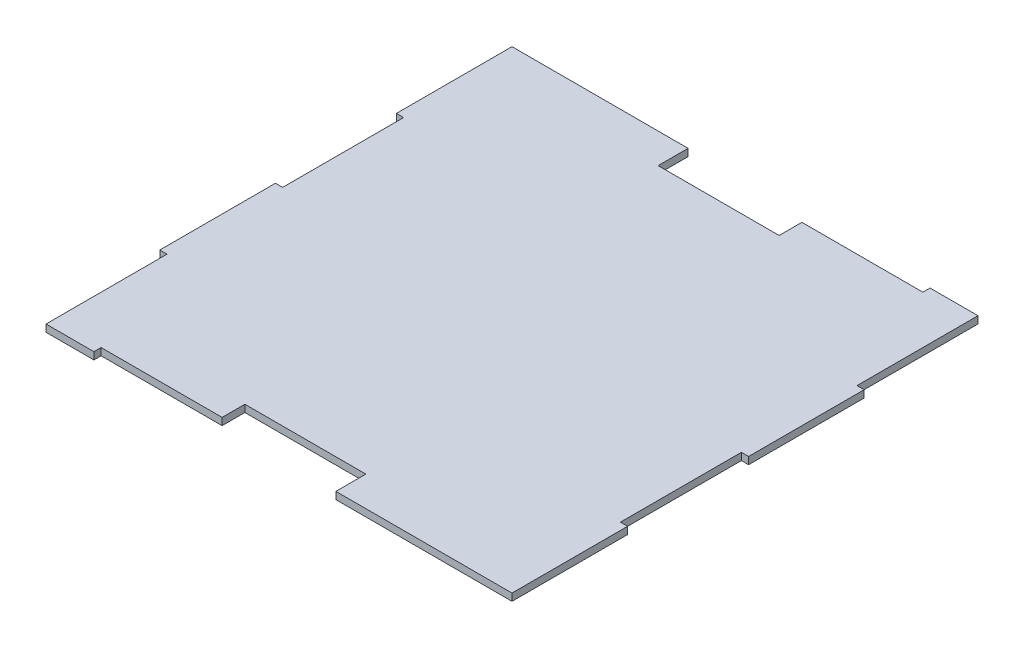
SolidWorks part; units mm, degrees
ref_plane "Front Plane" through (0, 0, 0) normal (0, 0, 1) x (1, 0, 0)
ref_plane "Top Plane" through (0, 0, 0) normal (0, 1, 0) x (1, 0, 0)
ref_plane "Right Plane" through (0, 0, 0) normal (1, 0, 0) x (0, 0, -1)
sketch "Sketch1" plane through (0, 0, 0) normal (0, 1, 0) x (1, 0, 0)
  line L1 (-197.5, -197.5) -> (197.5, -197.5)
  line L2 (-197.5, -197.5) -> (-197.5, 197.5)
  line L3 (-197.5, 197.5) -> (197.5, 197.5)
  line L4 (197.5, -197.5) -> (197.5, 197.5)
  line L5 (-197.5, -197.5) -> (197.5, 197.5) construction
  line L6 (-197.5, 197.5) -> (197.5, -197.5) construction
  line L7 (-50.5, 222.5) -> (50.5, 222.5)
  line L8 (-50.5, 222.5) -> (-50.5, 172.5)
  line L9 (-50.5, 172.5) -> (50.5, 172.5)
  line L10 (50.5, 222.5) -> (50.5, 172.5)
  line L11 (-50.5, 222.5) -> (50.5, 172.5) construction
  line L12 (-50.5, 172.5) -> (50.5, 222.5) construction
  line L13 (-50.5, -222.5) -> (50.5, -222.5)
  line L14 (-50.5, -222.5) -> (-50.5, -172.5)
  line L15 (-50.5, -172.5) -> (50.5, -172.5)
  line L16 (50.5, -222.5) -> (50.5, -172.5)
  line L17 (-50.5, -222.5) -> (50.5, -172.5) construction
  line L18 (-50.5, -172.5) -> (50.5, -222.5) construction
  line L43 (50.5, 197.5) -> (151.5, 197.5)
  line L44 (50.5, 197.5) -> (50.5, 191.5)
  line L45 (50.5, 191.5) -> (151.5, 191.5)
  line L46 (151.5, 197.5) -> (151.5, 191.5)
  line L47 (-50.5, -197.5) -> (-151.5, -197.5)
  line L48 (-50.5, -197.5) -> (-50.5, -191.5)
  line L49 (-50.5, -191.5) -> (-151.5, -191.5)
  line L50 (-151.5, -197.5) -> (-151.5, -191.5)
  line L51 (-197.5, -197.5) -> (-191.5, -197.5)
  line L52 (-197.5, -197.5) -> (-197.5, -96.5)
  line L53 (-197.5, -96.5) -> (-191.5, -96.5)
  line L54 (-191.5, -197.5) -> (-191.5, -96.5)
  line L55 (-197.5, 0) -> (-191.5, 0)
  line L56 (-197.5, 0) -> (-197.5, 101)
  line L57 (-197.5, 101) -> (-191.5, 101)
  line L58 (-191.5, 0) -> (-191.5, 101)
  line L59 (197.5, 197.5) -> (191.5, 197.5)
  line L60 (197.5, 197.5) -> (197.5, 96.5)
  line L61 (197.5, 96.5) -> (191.5, 96.5)
  line L62 (191.5, 197.5) -> (191.5, 96.5)
  line L63 (197.5, 0) -> (191.5, 0)
  line L64 (197.5, 0) -> (197.5, -101)
  line L65 (197.5, -101) -> (191.5, -101)
  line L66 (191.5, 0) -> (191.5, -101)
  point P0 (0, 0)
  point P6 (0, 197.5)
  point P11 (0, -197.5)
  dimension "D1" = 395
  dimension "D2" = 101
  dimension "D3" = 50
  dimension "D4" = 101
  dimension "D5" = 6
extrude "Boss-Extrude1" add sketch "Sketch1" along normal blind 6 contours L1 L14 L15 L16 L56 L4 L63 L66 L65 L3 L10 L9 L8 L54 L53 L2 L62 L61 region at (0, 0, 0)
